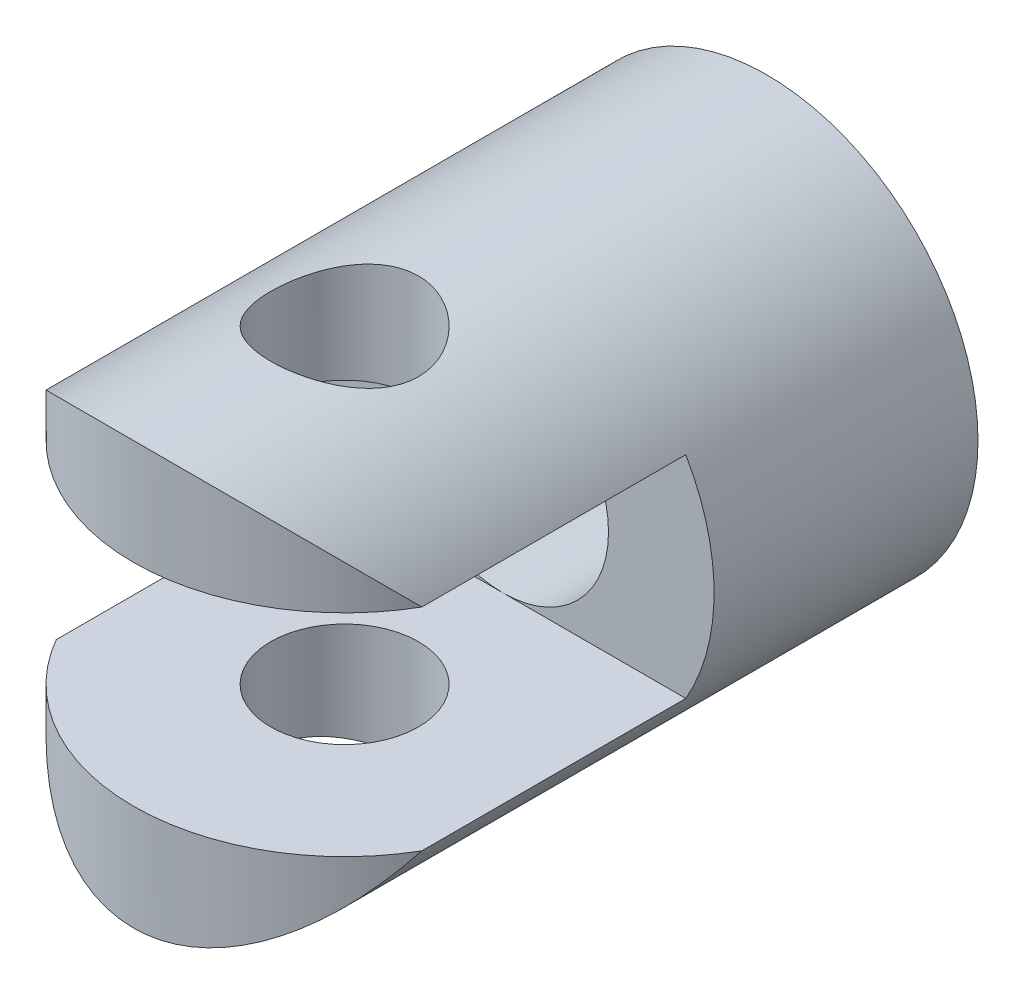
SolidWorks part; units mm, degrees
ref_plane "Płaszczyzna przednia" through (0, 0, 0) normal (0, 0, 1) x (1, 0, 0)
ref_plane "Płaszczyzna górna" through (0, 0, 0) normal (0, 1, 0) x (1, 0, 0)
ref_plane "Płaszczyzna prawa" through (0, 0, 0) normal (1, 0, 0) x (0, 0, -1)
sketch "Szkic1" plane through (0, 0, 0) normal (0, 0, 1) x (1, 0, 0)
  circle A0 centre (0, 0) radius 10
  circle A1 centre (0, 0) radius 20
  dimension "D1" = 20
extrude "Dodanie-wyciągnięcie1" add sketch "Szkic1" along normal blind 60
sketch "Szkic2" plane through (0, 0, 0) normal (0, 1, 0) x (1, 0, 0)
  line L1 (-20, 0) -> (20, 0)
  line L2 (-20, 0) -> (-20, -60)
  line L3 (-20, -60) -> (20, -60)
  line L4 (20, 0) -> (20, -60)
  circle A1 centre (0, -40) radius 20
  circle A2 centre (0, -40) radius 7
extrude "Wytnij-wyciągnięcie1" cut sketch "Szkic2" against normal blind 60 and the other way blind 60 contours A1 L2 L3 | A1 L3 L4 | A2 region at (-15.5326, 0, 55.5326) region at (15.5326, 0, 55.5326) region at (0, 0, 40)
ref_plane "Płaszczyzna1" through (0, 0, 60) normal (0, 0, 1) x (1, 0, 0)
sketch "Szkic3" plane through (0, 0, 60) normal (0, 0, 1) x (1, 0, 0)
  line L1 (21.6945, -10) -> (-21.6945, -10)
  line L2 (21.6945, -10) -> (21.6945, 10)
  line L3 (21.6945, 10) -> (-21.6945, 10)
  line L4 (-21.6945, -10) -> (-21.6945, 10)
  line L5 (21.6945, -10) -> (-21.6945, 10) construction
  line L6 (21.6945, 10) -> (-21.6945, -10) construction
  point P0 (0, 0)
extrude "Wytnij-wyciągnięcie2" cut sketch "Szkic3" against normal blind 35
